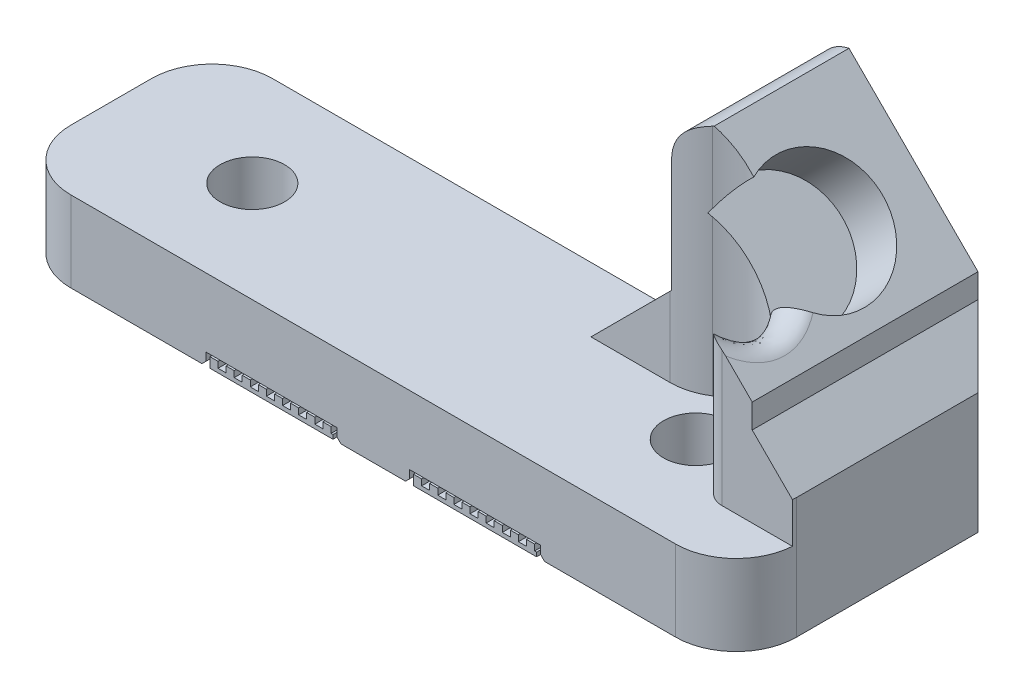
SolidWorks part; units mm, degrees
ref_plane "前视基准面" through (0, 0, 0) normal (0, 0, 1) x (1, 0, 0)
ref_plane "上视基准面" through (0, 0, 0) normal (0, 1, 0) x (1, 0, 0)
ref_plane "右视基准面" through (0, 0, 0) normal (1, 0, 0) x (0, 0, -1)
other "Configuration Table"
sketch "草图1" plane through (0, 0, 0) normal (0, 1, 0) x (1, 0, 0)
  line L1 (0, 0) -> (36, 0)
  line L2 (0, 0) -> (0, -10)
  line L3 (0, -10) -> (36, -10)
  line L4 (36, 0) -> (36, -10)
  circle A0 centre (7, -5) radius 1.6
  circle A1 centre (29, -5) radius 1.6
  point P9 (18, 0)
  point P10 (0, -5)
  dimension "D3" = 3.2
  dimension "D4" = 3.2
  dimension "D1" = 36
  dimension "D2" = 10
  dimension "D5" = 22
  dimension "D6" = 11
  dimension "D7" = 0
extrude "凸台-拉伸1" add sketch "草图1" along normal blind 4
sketch "草图2" plane through (0, 4, 0) normal (0, 1, 0) x (1, 0, 0)
  line L0 (36, 0) -> (0, 0) construction
  line L1 (26, 0) -> (34, 0)
  line L2 (26, 0) -> (26, 4)
  line L3 (26, 4) -> (34, 4)
  line L4 (34, 0) -> (34, 4)
  line L5 (36, -10) -> (36, 0) construction
  dimension "D1" = 4
  dimension "D2" = 10
  dimension "D3" = 2
extrude "凸台-拉伸2" add sketch "草图2" against normal blind 4
sketch "草图3" plane through (0, 4, 0) normal (0, 1, 0) x (1, 0, 0)
  line L0 (0, -10) -> (36, -10) construction
  line L1 (34, 4) -> (26, 4)
  line L2 (34, 4) -> (34, -7.2)
  line L3 (34, -7.2) -> (26, -7.2)
  line L4 (26, 4) -> (26, -7.2)
  dimension "D1" = 2.8
extrude "凸台-拉伸3" add sketch "草图3" along normal blind 5.2
sketch "草图4" plane through (0, 0, -4) normal (0, 0, -1) x (-1, 0, 0)
  line L0 (-34, 9.2) -> (-27.6, 15.6)
  line L1 (-27.6, 15.6) -> (-27.6, 9.2)
  line L2 (-27.6, 9.2) -> (-34, 9.2)
  dimension "D1" = 90
  dimension "D2" = 45
  dimension "D3" = 6.4
extrude "凸台-拉伸4" add sketch "草图4" against normal up to surface (11.2 mm away) up to face at (30, 6.6, 7.2)
sketch "草图6" plane through (0, 9.2, 0) normal (0, 1, 0) x (1, 0, 0)
  line L0 (26, -7.2) -> (27.6, -7.2) construction
  line L1 (26, 4) -> (27.6, 4)
  line L2 (26, 4) -> (26, -7.2)
  line L3 (26, -7.2) -> (27.6, -7.2)
  line L4 (27.6, 4) -> (27.6, -7.2)
  dimension "D1" = 0
extrude "凸台-拉伸5" add sketch "草图6" along normal up to vertex (6.4 mm away) up to point (27.6, 15.6, 7.2)
sketch "草图7" plane through (0, 4, 0) normal (0, 1, 0) x (1, 0, 0)
  line L0 (26, 0) -> (26, -7.2) construction
  line L1 (27.4348, -7.2) -> (26, -7.2)
  line L3 (26.9875, -3.2) -> (26, -3.2)
  line L4 (26, -7.2) -> (26, -3.2)
  arc A0 (27.4348, -7.2) -> (26.9875, -3.2) centre (29, -5) ccw
  dimension "D1" = 5.4
  dimension "D2" = 4
extrude "切除-拉伸2" cut sketch "草图7" along normal blind 12
sketch "草图5" plane through (21.6, 21.6, 0) normal (0.7071, 0.7071, 0) x (0.7071, -0.7071, 0)
  line L1 (17.5362, -7.2) -> (17.5362, 4) construction
  line L2 (8.4853, 4) -> (17.5362, 4) construction
  circle A0 centre (13.5362, -1) radius 3.1
  dimension "D2" = 6.2
  dimension "D1" = 5
  dimension "D3" = 4
extrude "切除-拉伸1" cut sketch "草图5" against normal blind 2.8
chamfer "倒角5" distance 4 angle 45 4 edges at (34, 4, 3.6) (34, 2, 0) (26, 4, 1.6) (26, 2, 0)
fillet "圆角8" radius 1 2 edges at (31.581, 11.619, 5.7929) (30.5652, 8.3174, 7.2)
fillet "圆角9" radius 3 3 edges at (36, 2, 10) (0, 2, 0) (0, 2, 10)
fillet "圆角10" radius 2 1 edges at (26, 15.6, -0.4)
fillet "圆角11" radius 3 1 edges at (26.9875, 9.6826, 3.2)
sketch "草图8" plane through (0, 0, 0) normal (0, -1, 0) x (-1, 0, 0)
  line L0 (-3, -10) -> (-33, -10) construction
  line L1 (-9.7, -10) -> (-16.2, -10)
  line L2 (-9.7, -10) -> (-9.7, 0)
  line L3 (-9.7, 0) -> (-16.2, 0)
  line L4 (-16.2, -10) -> (-16.2, 0)
  line L5 (-34, 4) -> (-26, 4) construction
  line L6 (-19.8, -10) -> (-26.3, -10)
  line L7 (-19.8, -10) -> (-19.8, 4)
  line L8 (-19.8, 4) -> (-26.3, 4)
  line L9 (-26.3, -10) -> (-26.3, 4)
  circle A0 centre (-29, -5) radius 1.6 construction
  circle A1 centre (-7, -5) radius 1.6 construction
  point P16 (0, 0)
  dimension "D1" = 6.5
  dimension "D2" = 6.5
  dimension "D3" = 2.7
  dimension "D4" = 2.7
extrude "切除-拉伸3" cut sketch "草图8" against normal blind 0.6
chamfer "倒角6" distance 0.2 angle 45 4 edges at (9.7, 0, 5) (26.3, 0, 3) (16.2, 0, 5) (19.8, 0, 5)
sketch "草图9" plane through (0, 0, 0) normal (0, -1, 0) x (1, 0, 0)
  line L0 (16.2, 10) -> (9.7, 10) construction
  line L1 (9.9, 10) -> (16, 10)
  line L2 (9.9, 10) -> (9.9, 0)
  line L3 (9.9, 0) -> (16, 0)
  line L4 (16, 10) -> (16, 0)
  line L5 (9.7, 0) -> (16.2, 0) construction
  line L6 (26.3, 10) -> (19.8, 10) construction
  line L7 (20, 10) -> (26.1, 10)
  line L8 (20, 10) -> (20, -4)
  line L9 (20, -4) -> (26.1, -4)
  line L10 (26.1, 10) -> (26.1, -4)
  line L12 (9.7, 10) -> (9.7, 0) construction
  line L14 (16.2, 0) -> (16.2, 10) construction
  line L15 (19.8, 10) -> (19.8, 0) construction
  line L18 (26.3, -4) -> (26.3, 10) construction
  point P22 (0, 0)
  dimension "D1" = 0.2
  dimension "D2" = 0.2
  dimension "D3" = 0.2
  dimension "D4" = 0.2
extrude "凸台-拉伸6" add sketch "草图9" against normal blind 0.2 separate body
sketch "草图10" plane through (0, 0.2, 0) normal (0, 1, 0) x (1, 0, 0)
  line L0 (16, -10) -> (9.9, -10) construction
  line L1 (9.9, 0) -> (10.3, 0)
  line L2 (9.9, 0) -> (9.9, -10)
  line L3 (9.9, -10) -> (10.3, -10)
  line L4 (10.3, 0) -> (10.3, -10)
  line L5 (26.1, -10) -> (20, -10) construction
  line L6 (20, 4) -> (20.4, 4)
  line L7 (20, 4) -> (20, -10)
  line L8 (20, -10) -> (20.4, -10)
  line L9 (20.4, 4) -> (20.4, -10)
  line L10 (10.7, 0) -> (10.7, -10)
  line L11 (10.7, 0) -> (11.1, 0)
  line L12 (11.1, 0) -> (11.1, -10)
  line L13 (10.7, -10) -> (11.1, -10)
  line L14 (20.8, 4) -> (20.8, -10)
  line L15 (20.8, 4) -> (21.2, 4)
  line L16 (21.2, 4) -> (21.2, -10)
  line L17 (20.8, -10) -> (21.2, -10)
  line L18 (11.5, 0) -> (11.5, -10)
  line L19 (11.5, 0) -> (11.9, 0)
  line L20 (11.9, 0) -> (11.9, -10)
  line L21 (11.5, -10) -> (11.9, -10)
  line L22 (21.6, 4) -> (21.6, -10)
  line L23 (21.6, 4) -> (22, 4)
  line L24 (22, 4) -> (22, -10)
  line L25 (21.6, -10) -> (22, -10)
  line L26 (12.3, 0) -> (12.3, -10)
  line L27 (12.3, 0) -> (12.7, 0)
  line L28 (12.7, 0) -> (12.7, -10)
  line L29 (12.3, -10) -> (12.7, -10)
  line L30 (22.4, 4) -> (22.4, -10)
  line L31 (22.4, 4) -> (22.8, 4)
  line L32 (22.8, 4) -> (22.8, -10)
  line L33 (22.4, -10) -> (22.8, -10)
  line L34 (13.1, 0) -> (13.1, -10)
  line L35 (13.1, 0) -> (13.5, 0)
  line L36 (13.5, 0) -> (13.5, -10)
  line L37 (13.1, -10) -> (13.5, -10)
  line L38 (23.2, 4) -> (23.2, -10)
  line L39 (23.2, 4) -> (23.6, 4)
  line L40 (23.6, 4) -> (23.6, -10)
  line L41 (23.2, -10) -> (23.6, -10)
  line L42 (13.9, 0) -> (13.9, -10)
  line L43 (13.9, 0) -> (14.3, 0)
  line L44 (14.3, 0) -> (14.3, -10)
  line L45 (13.9, -10) -> (14.3, -10)
  line L46 (24, 4) -> (24, -10)
  line L47 (24, 4) -> (24.4, 4)
  line L48 (24.4, 4) -> (24.4, -10)
  line L49 (24, -10) -> (24.4, -10)
  line L50 (14.7, 0) -> (14.7, -10)
  line L51 (14.7, 0) -> (15.1, 0)
  line L52 (15.1, 0) -> (15.1, -10)
  line L53 (14.7, -10) -> (15.1, -10)
  line L54 (24.8, 4) -> (24.8, -10)
  line L55 (24.8, 4) -> (25.2, 4)
  line L56 (25.2, 4) -> (25.2, -10)
  line L57 (24.8, -10) -> (25.2, -10)
  line L58 (15.5, 0) -> (15.5, -10)
  line L59 (15.5, 0) -> (15.9, 0)
  line L60 (15.9, 0) -> (15.9, -10)
  line L61 (15.5, -10) -> (15.9, -10)
  line L62 (25.6, 4) -> (25.6, -10)
  line L63 (25.6, 4) -> (26, 4)
  line L64 (26, 4) -> (26, -10)
  line L65 (25.6, -10) -> (26, -10)
  dimension "D1" = 0.4
  dimension "D2" = 0.4
  dimension "D3" = 8
extrude "凸台-拉伸7" add sketch "草图10" along normal blind 0.3
equation "\"D5@草图1\"=26-4"
equation "\"D6@草图1\"=\"D5@草图1\"/2"
